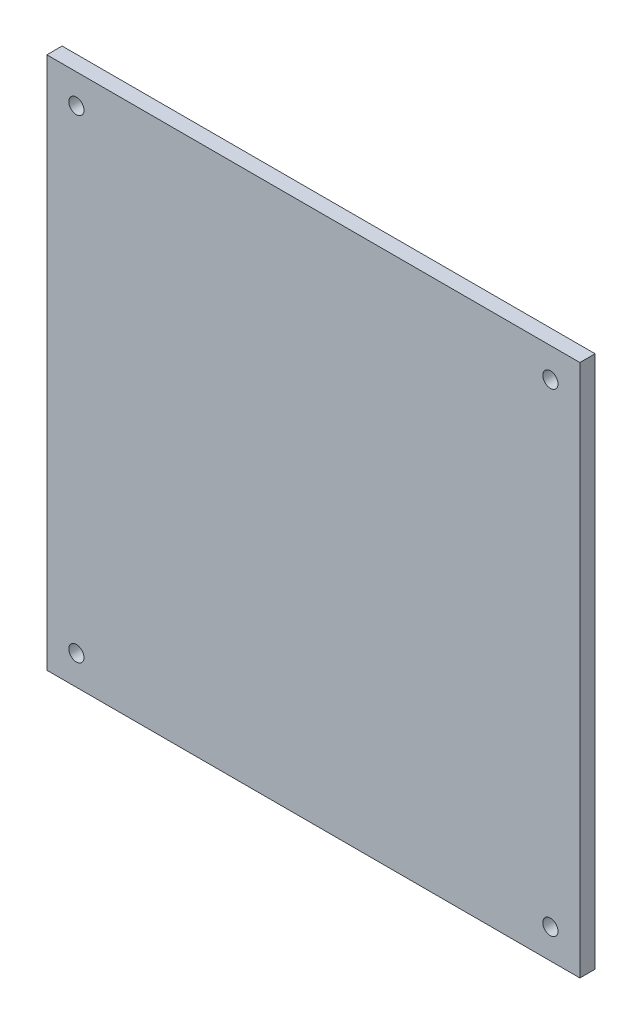
SolidWorks part; units mm, degrees
material "Polyurethane Foam Flexible"
ref_plane "Front" through (0, 0, 0) normal (0, 0, 1) x (1, 0, 0)
ref_plane "Top" through (0, 0, 0) normal (0, 1, 0) x (1, 0, 0)
ref_plane "Right" through (0, 0, 0) normal (1, 0, 0) x (0, 0, -1)
sketch "Sketch2" plane through (0, 0, 0) normal (0, 0, 1) x (1, 0, 0)
  line L1 (65.8661, -38.7717) -> (205.8661, -38.7717)
  line L2 (65.8661, -38.7717) -> (65.8661, 101.2283)
  line L3 (65.8661, 101.2283) -> (205.8661, 101.2283)
  line L4 (205.8661, -38.7717) -> (205.8661, 101.2283)
  circle A0 centre (73.6161, 93.4783) radius 2
  circle A1 centre (198.1161, 93.4783) radius 2
  circle A2 centre (198.1161, -31.0217) radius 2
  circle A3 centre (73.6161, -31.0217) radius 2
  dimension "D1" = 140
  dimension "D2" = 140
base flange "Base-Flange2" sketch "Sketch2" thickness 4 reverse thickness direction no parameters "D1"=1.651
sketch "Bend-Lines3" [suppressed] plane through (0, 0, 0) normal (0, 1, 0) x (1, 0, 0)
sketch "Bounding-Box3" [suppressed] plane through (0, 0, 0) normal (0, 1, 0) x (1, 0, 0)
sheet metal parameters "Sheet-Metal2" thickness 4 parameters "D1"=1.651
flat pattern "Flat-Pattern2" [suppressed]
sketch "Bend-Lines4" plane through (0, 0, 0) normal (0, 1, 0) x (1, 0, 0)
sketch3d "Bounding-Box4" [suppressed]
  line L0 (65.8661, -38.7717, 0) -> (205.8661, -38.7717, 0) construction
  line L1 (65.8661, 101.2283, 0) -> (205.8661, 101.2283, 0) construction
  line L2 (65.8661, -38.7717, 0) -> (65.8661, 101.2283, 0) construction
  line L3 (205.8661, -38.7717, 0) -> (205.8661, 101.2283, 0) construction
